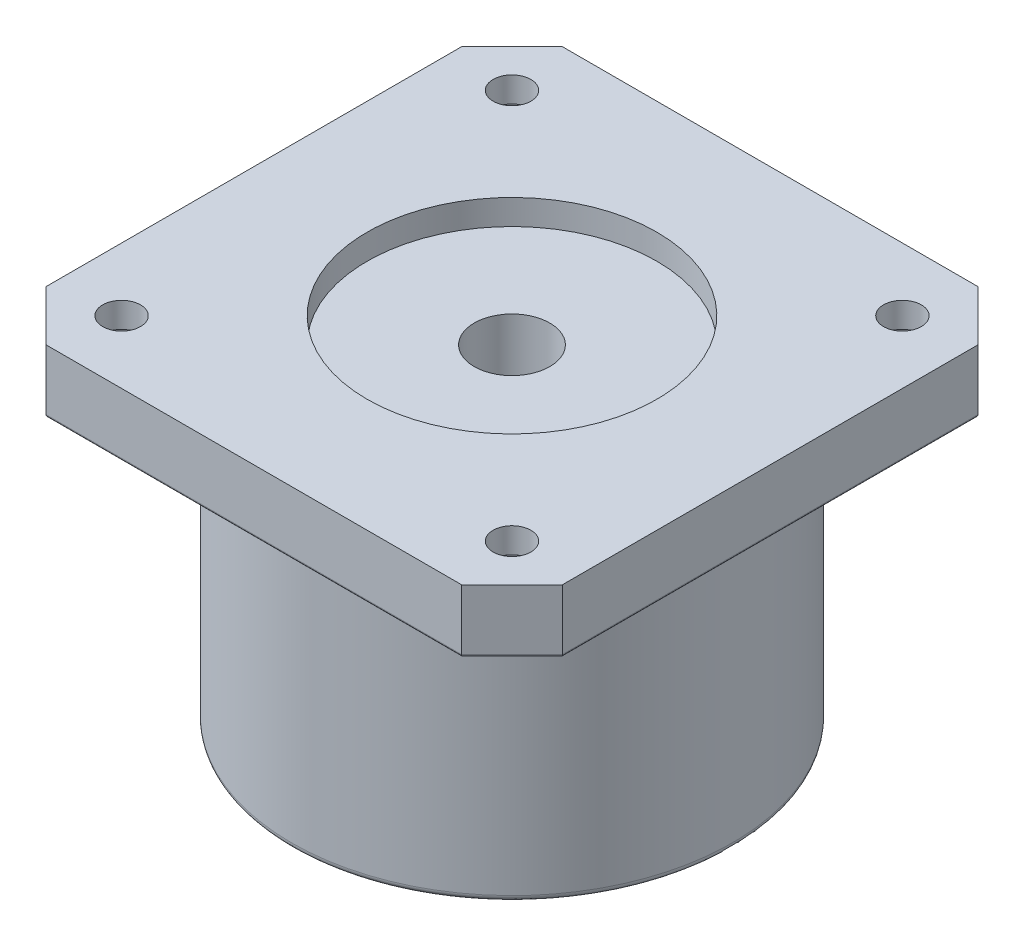
SolidWorks part; units mm, degrees
ref_plane "Front Plane" through (0, 0, 0) normal (0, 0, 1) x (1, 0, 0)
ref_plane "Top Plane" through (0, 0, 0) normal (0, 1, 0) x (1, 0, 0)
ref_plane "Right Plane" through (0, 0, 0) normal (1, 0, 0) x (0, 0, -1)
sketch "Sketch1" plane through (0, 0, 0) normal (0, 1, 0) x (1, 0, 0)
  line L1 (0, 0) -> (41, 0)
  line L2 (0, 0) -> (0, 41)
  line L3 (0, 41) -> (41, 41)
  line L4 (41, 0) -> (41, 41)
  dimension "D1" = 41
  dimension "D2" = 41
extrude "Boss-Extrude1" add sketch "Sketch1" along normal blind 5
sketch "Sketch2" plane through (0, 5, 0) normal (0, 1, 0) x (1, 0, 0)
  line L0 (0, 0) -> (0, 4)
  line L1 (0, 41) -> (0, 0) construction
  line L2 (0, 4) -> (4, 0)
  line L3 (0, 0) -> (41, 0) construction
  line L4 (4, 0) -> (0, 0)
  line L5 (37, 0) -> (41, 4)
  line L6 (41, 0) -> (41, 41) construction
  line L7 (41, 4) -> (41, 0)
  line L8 (41, 0) -> (37, 0)
  line L9 (37, 41) -> (41, 41)
  line L10 (41, 41) -> (0, 41) construction
  line L11 (41, 41) -> (41, 37)
  line L12 (41, 37) -> (37, 41)
  line L13 (0, 42.1095) -> (0, 41)
  line L14 (0, 41) -> (0, 37)
  line L15 (0, 37) -> (4, 41)
  line L16 (4, 41) -> (0, 41)
  line M4 (0, 41) -> (0, 0)
  line M5 (0, 0) -> (41, 0)
  line M6 (41, 0) -> (41, 41)
  line M7 (41, 41) -> (0, 41)
  dimension "D1" = 4
  dimension "D2" = 4
  dimension "D3" = 4
  dimension "D4" = 4
  dimension "D5" = 4
  dimension "D6" = 4
  dimension "D7" = 4
  dimension "D8" = 4
extrude "Cut-Extrude2" cut sketch "Sketch2" against normal blind 5 contours L2 M4 M5 | L15 M4 M7 | L12 M6 M7 | L5 M5 M6 region at (1.3333, 5, -1.3333) region at (1.3333, 5, -39.6667) region at (39.6667, 5, -1.3333) region at (39.6667, 5, -39.6667)
sketch "Sketch4" plane through (0, 5, 0) normal (0, 1, 0) x (1, 0, 0)
  line L0 (0, 37) -> (0, 4) construction
  line L1 (4, 0) -> (37, 0) construction
  circle A0 centre (20.5, 20.5) radius 11.5
  dimension "D1" = 23
  dimension "D2" = 20.5
  dimension "D3" = 20.5
extrude "Cut-Extrude3" cut sketch "Sketch4" against normal blind 2
sketch "Sketch5" plane through (0, 5, 0) normal (0, 1, 0) x (1, 0, 0)
  circle A4 centre (20.5, 20.5) radius 3
  point P2 (20.5, 20.5)
  dimension "D6" = 6
sketch "Sketch6" plane through (0, 0, 0) normal (0, -1, 0) x (1, 0, 0)
  circle A0 centre (20.5, -20.5) radius 17.5
  dimension "D1" = 35
extrude "Boss-Extrude2" add sketch "Sketch6" along normal blind 23
fillet "Fillet1" radius 0.2 8 edges at (2, 0, -39) (0, 0, -20.5) (2, 0, -2) (20.5, 0, -41) (39, 0, -39) (41, 0, -20.5) (39, 0, -2) (20.5, 0, 0)
fillet "Fillet2" radius 0.5 1 edges at (20.5, -23, -38)
sketch "Sketch13" plane through (0, -23, 0) normal (0, -1, 0) x (-1, 0, 0)
  circle A0 centre (-20.5, 20.5) radius 11
  dimension "D1" = 22
extrude "Boss-Extrude3" add sketch "Sketch13" along normal blind 2 contours A0
extrude "Cut-Extrude9" cut sketch "Sketch5" against normal through all contours A4
sketch "Sketch14" plane through (0, -23, 0) normal (0, -1, 0) x (-1, 0, 0)
  line L0 (-20.5, 20.5) -> (-20.5, -1.0982) construction
  circle A0 centre (-20.5, 6.5) radius 2.5
  circle A2 centre (-34.5, 20.5) radius 2.5
  circle A3 centre (-20.5, 34.5) radius 2.5
  circle A4 centre (-6.5, 20.5) radius 2.5
  point P14 (-20.5, 20.5)
  dimension "D2" = 5
  dimension "D1" = 14
  dimension "D3" = 4
sketch "Sketch15" plane through (0, -23, 0) normal (0, -1, 0) x (-1, 0, 0)
  circle A1 centre (-30.3995, 10.6005) radius 1.3553
  circle A3 centre (-30.3995, 30.3995) radius 1.3553
  circle A5 centre (-10.6005, 30.3995) radius 1.3553
  circle A7 centre (-10.6005, 10.6005) radius 1.3553
  point P21 (-20.5, 20.5)
extrude "Cut-Extrude10" cut sketch "Sketch14" against normal blind 5
extrude "Cut-Extrude11" cut sketch "Sketch15" against normal blind 5
sketch "Sketch16" plane through (0, 0, 0) normal (0, -1, 0) x (-1, 0, 0)
  circle A0 centre (-5, 5) radius 2.5
  circle A1 centre (-36, 5) radius 2.5
  circle A2 centre (-5, 36) radius 2.5
  circle A3 centre (-36, 36) radius 2.5
  dimension "D1" = 5
  dimension "D2" = 5
  dimension "D3" = 15.5
  dimension "D4" = 15.5
  dimension "D5" = 15.5
  dimension "D6" = 15.5
  dimension "D7" = 2
extrude "Cut-Extrude12" cut sketch "Sketch16" against normal blind 3
sketch "Sketch17" plane through (0, 3, 0) normal (0, -1, 0) x (-1, 0, 0)
  circle A0 centre (-5, 5) radius 1.5
  circle A1 centre (-36, 5) radius 1.5
  circle A2 centre (-5, 36) radius 1.5
  circle A3 centre (-36, 36) radius 1.5
  dimension "D1" = 3
  dimension "D4" = 3
  dimension "D2" = 15.5
  dimension "D3" = 15.5
  dimension "D5" = 2
extrude "Cut-Extrude13" cut sketch "Sketch17" against normal through all
